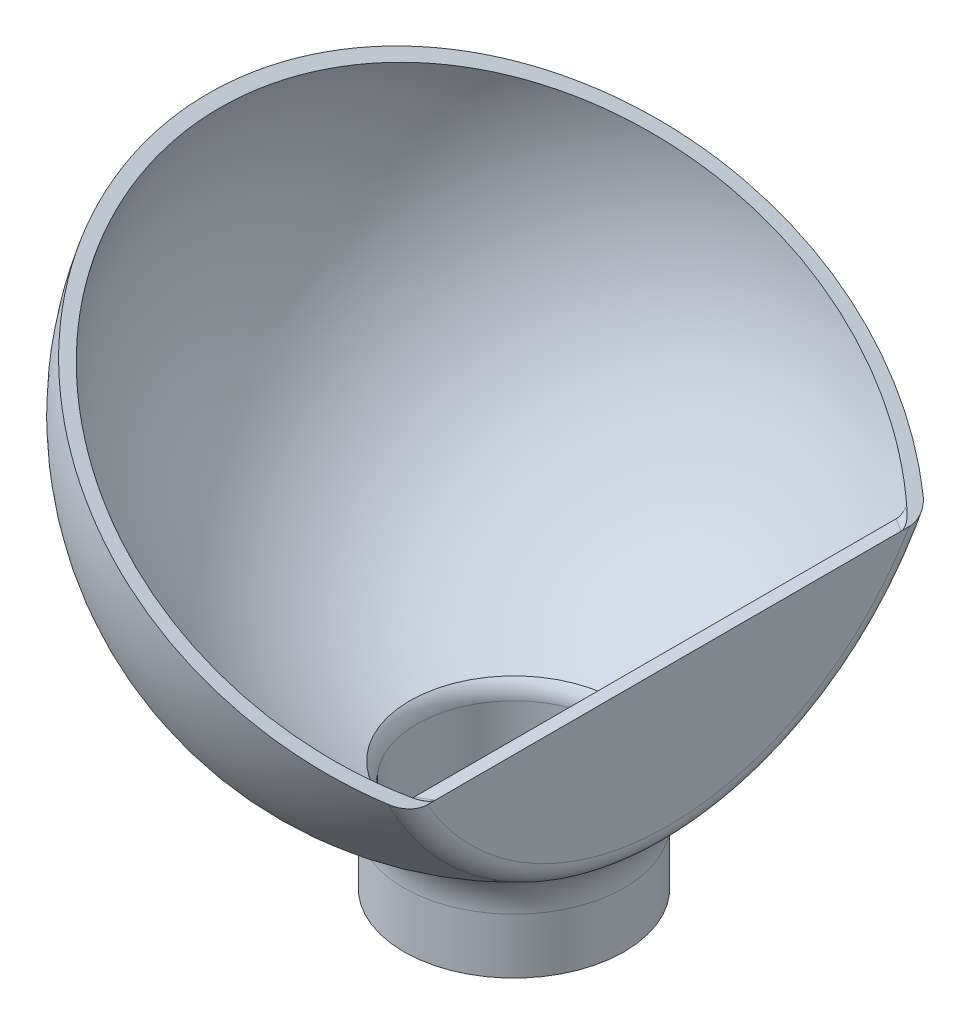
SolidWorks part; units mm, degrees
ref_plane "Front Plane" through (0, 0, 0) normal (0, 0, 1) x (1, 0, 0)
ref_plane "Top Plane" through (0, 0, 0) normal (0, 1, 0) x (1, 0, 0)
ref_plane "Right Plane" through (0, 0, 0) normal (1, 0, 0) x (0, 0, -1)
sketch "Sketch5" plane through (0, 0, 0) normal (0, 1, 0) x (1, 0, 0)
  line L0 (-75, 0) -> (-72, 0)
  line L1 (72, 0) -> (75, 0)
  arc A0 (-75, 0) -> (75, 0) centre (0, 0) ccw
  arc A1 (-72, 0) -> (72, 0) centre (0, 0) ccw
  dimension "D1" = 150
  dimension "D2" = 3
revolve "Revolve3" add sketch "Sketch5" angle 360 about L0
ref_plane "Plane3" through (0, -68, 0) normal (0, 1, 0) x (1, 0, 0)
sketch "Sketch6" plane through (0, -68, 0) normal (0, 1, 0) x (1, 0, 0)
  line L9 (-92.0092, -76.3271) -> (89.9394, -76.3271)
  line L10 (-92.0092, -76.3271) -> (-92.0092, 92.0952)
  line L11 (-92.0092, 92.0952) -> (89.9394, 92.0952)
  line L12 (89.9394, -76.3271) -> (89.9394, 92.0952)
  point P4 (89.9394, 92.0952)
  point P5 (-92.0092, -76.3271)
extrude "Cut-Extrude1" cut sketch "Sketch6" against normal up to surface (50.1934 mm away)
ref_plane "Plane4" through (35, 0, 0) normal (1, 0, 0) x (0, 0, -1)
sketch "Sketch7" plane through (35, 0, 0) normal (1, 0, 0) x (0, 0, -1)
  line L1 (-84.4115, -78.896) -> (89.3472, -78.896)
  line L2 (-84.4115, -78.896) -> (-84.4115, 82.5158)
  line L3 (-84.4115, 82.5158) -> (89.3472, 82.5158)
  line L4 (89.3472, -78.896) -> (89.3472, 82.5158)
  point P4 (-84.4115, -78.896)
  point P5 (89.3472, 82.5158)
extrude "Cut-Extrude4" cut sketch "Sketch7" along normal up to surface up to face at (0, -68, -31.6386)
sketch "Sketch8" plane through (0, 0, 0) normal (0, 1, 0) x (1, 0, 0)
  line L0 (0, 27.1728) -> (0, -32.4527) construction
ref_plane "Plane5" through (0, 0, 0) normal (-0.5, -0.866, 0) x (0, 0, 1)
ref_plane "Plane6" through (-5, -8.6603, 0) normal (-0.5, -0.866, 0) x (0, 0, 1)
sketch "Sketch12" plane through (-5, -8.6603, 0) normal (-0.5, -0.866, 0) x (0, 0, 1)
  line L1 (93.1626, 176.5404) -> (-99.5972, 176.5404)
  line L2 (93.1626, 176.5404) -> (93.1626, -157.2552)
  line L3 (93.1626, -157.2552) -> (-99.5972, -157.2552)
  line L4 (-99.5972, 176.5404) -> (-99.5972, -157.2552)
extrude "Cut-Extrude5" cut sketch "Sketch12" against normal up to surface up to face at (35, 0, 66.3325)
sketch "Sketch14" plane through (35, 0, 0) normal (1, 0, 0) x (0, 0, -1)
  line L0 (-58.238, -31.7543) -> (58.238, -31.7543)
  arc A0 (-58.238, -31.7543) -> (58.238, -31.7543) centre (0, 0) ccw
extrude "Boss-Extrude2" add sketch "Sketch14" against normal blind 3
sketch "Sketch15" plane through (0, -68, 0) normal (0, -1, 0) x (1, 0, 0)
  circle A0 centre (0, 0) radius 25
extrude "Boss-Extrude3" add sketch "Sketch15" along normal blind 25
sketch "Sketch16" plane through (0, -68, 0) normal (0, 1, 0) x (1, 0, 0)
  circle A0 centre (0, 0) radius 22
extrude "Cut-Extrude6" cut sketch "Sketch16" against normal through all
fillet "Fillet1" radius 15 1 edges at (0, -68, -25)
fillet "Fillet3" radius 5 1 edges at (35, -66.3325, 0)
fillet "Fillet4" radius 2 2 edges at (33.5124, -31.7543, -55.2502) (33.5124, -31.7543, 55.2502)
fillet "Fillet5" radius 5 1 edges at (0, -68, 22)
